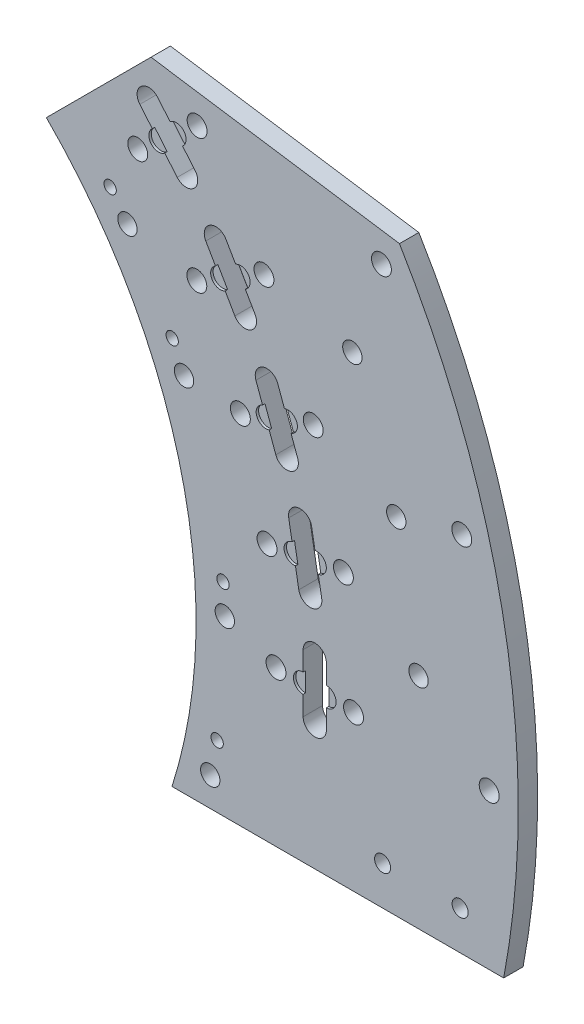
SolidWorks part; units mm, degrees
ref_plane "Front Plane" through (0, 0, 0) normal (0, 0, 1) x (1, 0, 0)
ref_plane "Top Plane" through (0, 0, 0) normal (0, 1, 0) x (1, 0, 0)
ref_plane "Right Plane" through (0, 0, 0) normal (1, 0, 0) x (0, 0, -1)
sketch "Sketch1" plane through (0, 0, 0) normal (0, 0, 1) x (1, 0, 0)
  line L0 (0, 0) -> (177.8, 0) construction
  line L1 (176.8984, 6.1774) -> (0, 0) construction
  line L2 (0, 0) -> (121.7947, 121.7947) construction
  line L3 (121.7947, 121.7947) -> (122.9173, 122.9173) construction
  line L4 (144.995, 101.5266) -> (0, 0) construction
  line L5 (0, 0) -> (163.5325, 67.7374) construction
  line L6 (167.4812, 0) -> (167.4812, -50.8) construction
  line L8 (159.5911, -50.8) -> (167.4812, -50.8) construction
  line L9 (172.1267, -41.275) -> (0, 0) construction
  line L10 (159.5911, -50.8) -> (268.2828, -50.8)
  line L11 (118.4271, 118.4271) -> (152.7152, 152.7152)
  line L12 (177.8, 0) -> (193.675, 0) construction
  line L13 (202.565, 0) -> (210.185, 0) construction
  line L14 (210.185, 0) -> (219.075, 0) construction
  line L15 (193.675, 0) -> (202.565, 0) construction
  line L16 (202.565, 0) -> (202.565, 9.525)
  line L17 (202.565, 0) -> (202.565, -9.525)
  line L18 (210.185, 9.525) -> (210.185, 0)
  line L19 (210.185, 0) -> (210.185, -9.525)
  line L20 (202.565, -9.525) -> (210.185, -9.525) construction
  line L21 (202.565, 9.525) -> (210.185, 9.525) construction
  line L22 (210.185, 9.525) -> (219.075, 0) construction
  line L23 (202.565, 9.525) -> (193.675, 0) construction
  line L24 (199.4876, 35.175) -> (201.1416, 25.7947)
  line L25 (199.4876, 35.175) -> (197.8336, 44.5553)
  line L26 (205.3378, 45.8785) -> (206.9918, 36.4982)
  line L27 (206.9918, 36.4982) -> (208.6458, 27.1179)
  line L28 (190.3488, 69.2813) -> (193.6066, 60.3307)
  line L29 (190.3488, 69.2813) -> (187.0911, 78.2319)
  line L30 (194.2516, 80.8381) -> (197.5093, 71.8875)
  line L31 (197.5093, 71.8875) -> (200.767, 62.9369)
  line L32 (175.4264, 101.2825) -> (180.1889, 93.0336)
  line L33 (175.4264, 101.2825) -> (170.6639, 109.5314)
  line L34 (177.263, 113.3414) -> (182.0255, 105.0925)
  line L35 (182.0255, 105.0925) -> (186.788, 96.8436)
  line L36 (155.1738, 130.2063) -> (161.2963, 122.9097)
  line L37 (155.1738, 130.2063) -> (149.0512, 137.5028)
  line L38 (154.8885, 142.4009) -> (161.0111, 135.1043)
  line L39 (161.0111, 135.1043) -> (167.1336, 127.8077)
  line L40 (0, 0) -> (193.675, 0) construction
  line L41 (0, 0) -> (190.7326, 33.6313) construction
  line L42 (0, 0) -> (254, 0) construction
  line L43 (254, 0) -> (263.525, 0) construction
  line L44 (254.5456, 68.2053) -> (0, 0) construction
  line L45 (152.7152, 152.7152) -> (234.123, 140.5088)
  line L46 (167.8212, 140.8187) -> (228.2193, 131.7625) construction
  line L47 (254.5456, 68.2053) -> (263.746, 70.6705) construction
  line L48 (0, 0) -> (240.3818, 21.0307) construction
  line L49 (0, 0) -> (240.3818, 21.0307) construction
  line L50 (0, 0) -> (233.0779, 62.453) construction
  line L51 (215.9, -50.8) -> (215.9, -25.4) construction
  line L52 (215.9, -25.4) -> (266.7, -25.4) construction
  line L53 (266.7, -25.4) -> (266.7, -50.8) construction
  line L54 (228.6, -38.1) -> (254, -38.1) construction
  line L55 (0, 0) -> (159.6519, 76.4361) construction
  line L56 (0, 0) -> (139.3238, 109.1792) construction
  line L57 (0, 0) -> (159.6519, 76.4361) construction
  line L58 (0, 0) -> (176.31, 15.6842) construction
  arc A0 (172.2437, 0) -> (121.7947, 121.7947) centre (0, 0) ccw construction
  arc A1 (173.8312, 0) -> (122.9173, 122.9173) centre (0, 0) ccw construction
  circle A2 centre (176.8984, 6.1774) radius 3.175
  circle A3 centre (144.995, 101.5266) radius 3.175
  circle A4 centre (163.5325, 67.7374) radius 3.175
  arc A5 (167.4812, 0) -> (118.4271, 118.4271) centre (0, 0) ccw
  arc A6 (167.4812, 0) -> (159.5911, -50.8) centre (0, 0) cw
  arc A7 (173.8312, 0) -> (166.2428, -50.8) centre (0, 0) cw construction
  circle A8 centre (172.1267, -41.275) radius 3.175
  circle A9 centre (193.675, 0) radius 9.525 construction
  circle A10 centre (219.075, 0) radius 9.525 construction
  arc A11 (202.565, -9.525) -> (210.185, -9.525) centre (206.375, -9.525) ccw
  arc A12 (202.565, 9.525) -> (210.185, 9.525) centre (206.375, 9.525) cw
  circle A13 centre (193.675, 0) radius 3.2639
  circle A14 centre (219.075, 0) radius 3.2639
  circle A15 centre (215.7468, 38.042) radius 3.2639
  arc A16 (201.1416, 25.7947) -> (208.6458, 27.1179) centre (204.8937, 26.4563) ccw
  arc A17 (197.8336, 44.5553) -> (205.3378, 45.8785) centre (201.5857, 45.2169) cw
  circle A18 centre (190.7326, 33.6313) radius 3.2639
  circle A19 centre (205.8632, 74.9281) radius 3.2639
  arc A20 (193.6066, 60.3307) -> (200.767, 62.9369) centre (197.1868, 61.6338) ccw
  arc A21 (187.0911, 78.2319) -> (194.2516, 80.8381) centre (190.6713, 79.535) cw
  circle A22 centre (181.995, 66.2408) radius 3.2639
  circle A23 centre (189.7245, 109.5375) radius 3.2639
  arc A24 (180.1889, 93.0336) -> (186.788, 96.8436) centre (183.4885, 94.9386) ccw
  arc A25 (170.6639, 109.5314) -> (177.263, 113.3414) centre (173.9635, 111.4364) cw
  circle A26 centre (167.7275, 96.8375) radius 3.2639
  circle A27 centre (167.8212, 140.8187) radius 3.2639
  arc A28 (161.2963, 122.9097) -> (167.1336, 127.8077) centre (164.215, 125.3587) ccw
  arc A29 (149.0512, 137.5028) -> (154.8885, 142.4009) centre (151.9699, 139.9519) cw
  circle A30 centre (148.3637, 124.4919) radius 3.2639
  circle A31 centre (263.525, 0) radius 3.2639
  circle A32 centre (254.5456, 68.2053) radius 3.2639
  circle A33 centre (228.2193, 131.7625) radius 3.2639
  arc A34 (234.123, 140.5088) -> (268.2828, -50.8) centre (0, 0) cw
  circle A36 centre (240.3818, 21.0307) radius 3.175
  circle A37 centre (233.0779, 62.453) radius 3.175
  circle A38 centre (218.6921, 101.9778) radius 3.175
  arc A39 (210.185, 0) -> (203.9537, -50.8) centre (0, 0) cw construction
  circle A40 centre (228.6, -38.1) radius 2.6289
  circle A41 centre (254, -38.1) radius 2.6289
  circle A42 centre (159.6519, 76.4361) radius 9.525 construction
  circle A43 centre (159.6519, 76.4361) radius 2.0193
  circle A44 centre (159.6519, 76.4361) radius 3.175 construction
  circle A45 centre (139.3238, 109.1792) radius 2.0193
  circle A46 centre (139.3238, 109.1792) radius 9.525 construction
  circle A47 centre (176.31, 15.6842) radius 2.0193
  circle A48 centre (176.31, 15.6842) radius 9.525 construction
  circle A49 centre (174.3917, -30.3106) radius 2.0193
  circle A50 centre (174.3917, -30.3106) radius 9.525 construction
  point P3 (172.2437, 0)
  point P96 (0, 0)
  point P114 (266.7, -38.1)
  point P121 (180.1889, -30.5819)
  point P124 (0, 0)
  point P132 (0, 0)
  point P133 (0, 0)
  point P134 (173.8312, -30.3106)
  dimension "D3" = 1.5875
  dimension "D4" = 6.35
  dimension "D5" = 2
  dimension "D7" = 10
  dimension "D8" = 6.35
  dimension "D9" = 6.35
  dimension "D11" = 6.35
  dimension "D13" = 6.35
  dimension "D15" = 19.05
  dimension "D16" = 7.62
  dimension "D17" = 19.05
  dimension "D21" = 15.875
  dimension "D22" = 6.5278
  dimension "D23" = 6.5278
  dimension "D28" = 6.5278
  dimension "D32" = 9.525
  dimension "D33" = 5
  dimension "D34" = 241.3
  dimension "D35" = 6.35
  dimension "D38" = 25.4
  dimension "D40" = 5.2578
  dimension "D41" = 5.2578
  dimension "D43" = 12.7
  dimension "D45" = 263.525
  dimension "D46" = 19.05
  dimension "D47" = 4.0386
  dimension "D48" = 6.35
  dimension "D1" = 177.8
  dimension "D2" = 5.5562
  dimension "D6" = 45
  dimension "D10" = 22.5
  dimension "D12" = 50.8
  dimension "D14" = 9.525
  dimension "D18" = 9.525
  dimension "D19" = 9.525
  dimension "D20" = 25.4
  dimension "D25" = 10
  dimension "D26" = 254
  dimension "D27" = 9.525
  dimension "D30" = 15
  dimension "D31" = 9.525
  dimension "D37" = 10
  dimension "D39" = 50.8
  dimension "D42" = 25.4
  dimension "D44" = 215.9
  dimension "D50" = 12.5
  dimension "D52" = 20.5
  dimension "D54" = 12.7
  dimension "D24" = 5
  dimension "D29" = 3
  dimension "D36" = 3
  dimension "D49" = 2
  dimension "D51" = 2
  dimension "D53" = 2
extrude "Boss-Extrude1" add sketch "Sketch1" along normal blind 6.35 contours A34 L45 L11 A5 A6 L10 A33 A32 A31 A30 A27 A26 A23 A22 A19 A18 A15 A14 A13 A8 A4 A3 A2 L16 A12 L18 L19 A11 L17 L25 A17 L26 region at (208.0179, 48.2023, 0)
sketch "Sketch2" plane through (0, 0, 6.35) normal (0, 0, 1) x (1, 0, 0)
  line L0 (202.565, -9.525) -> (202.565, 9.525) construction
  line L1 (210.185, 9.525) -> (210.185, -9.525) construction
  line L2 (0, 0) -> (202.565, 0) construction
  line L3 (0, 0) -> (199.4876, 35.175) construction
  circle A0 centre (202.565, 0) radius 3.175
  circle A1 centre (210.185, 0) radius 3.175
  circle A2 centre (199.4876, 35.175) radius 3.175
  circle A3 centre (206.9918, 36.4982) radius 3.175
  circle A4 centre (190.3488, 69.2813) radius 3.175
  circle A5 centre (197.5093, 71.8875) radius 3.175
  circle A6 centre (175.4264, 101.2825) radius 3.175
  circle A7 centre (182.0255, 105.0925) radius 3.175
  circle A8 centre (155.1738, 130.2063) radius 3.175
  circle A9 centre (161.0111, 135.1043) radius 3.175
  dimension "D1" = 6.35
  dimension "D2" = 6.35
  dimension "D4" = 10
  dimension "D3" = 5
extrude "Cut-Extrude1" cut sketch "Sketch2" against normal blind 0.7937
sketch "Sketch3" plane through (0, 0, 6.35) normal (0, 0, 1) x (1, 0, 0)
  line L0 (0, 0) -> (167.4812, 0) construction
  line L1 (159.5911, -50.8) -> (159.5911, 0) construction
  arc A0 (159.5911, -50.8) -> (118.4271, 118.4271) centre (0, 0) ccw construction
  dimension "D1" = 7.8901
